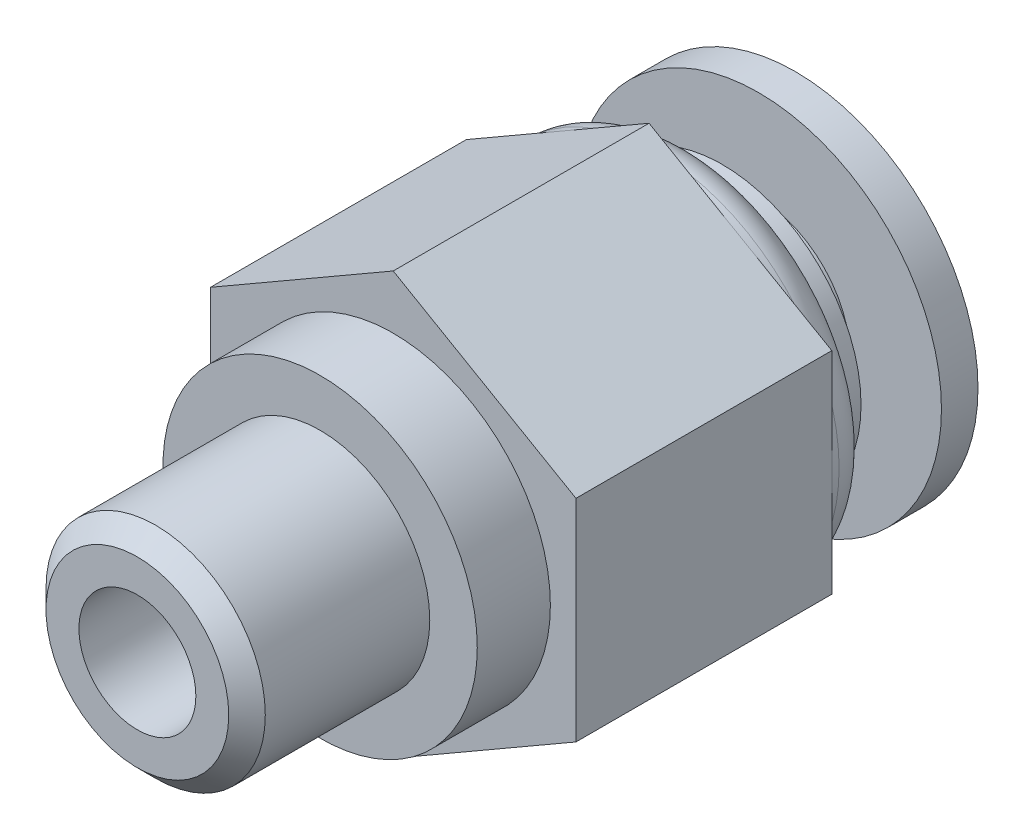
SolidWorks part; units mm, degrees
note: The reader was unsure of these and kept them because the rebuilt part matched: shared geometry of "Эскиз1<4>", "Эскиз1<5>", "Эскиз1<6>", "Эскиз1<8>", "Эскиз1<10>", "Эскиз1<11>".
material "Plain Carbon Steel"
ref_plane "Спереди" through (0, 0, 0) normal (0, 0, 1) x (1, 0, 0)
ref_plane "Сверху" through (0, 0, 0) normal (0, 1, 0) x (1, 0, 0)
ref_plane "Справа" through (0, 0, 0) normal (1, 0, 0) x (0, 0, -1)
sketch "Эскиз1" plane through (0, 0, 0) normal (0, 0, 1) x (1, 0, 0)
  line L3 (0, 5.7735) -> (-5, 2.8868)
  line L4 (-5, 2.8868) -> (-5, -2.8868)
  line L5 (-5, -2.8868) -> (0, -5.7735)
  line L6 (0, -5.7735) -> (5, -2.8868)
  line L7 (5, -2.8868) -> (5, 2.8868)
  line L8 (5, 2.8868) -> (0, 5.7735)
  circle A0 centre (0, 0) radius 1.6
  circle A1 centre (0, 0) radius 3
  circle A2 centre (0, 0) radius 5 construction
  circle A3 centre (0, 0) radius 5
  circle A4 centre (0, 0) radius 4.3
  circle A5 centre (0, 0) radius 3
  circle A6 centre (0, 0) radius 3.8
  dimension "D1" = 3.2
  dimension "D2" = 6
  dimension "D3" = 6
  dimension "D4" = 8.6
  dimension "D5" = 10
  dimension "D6" = 10
extrude "Бобышка-Вытянуть2" add sketch "Эскиз1" along normal blind 7 contours L3 L4 L5 L6 L7 L8
extrude "Бобышка-Вытянуть3" add sketch "Эскиз1<4>" against normal blind 1.2 contours A3
sketch "Эскиз1<4>" plane through (0, 0, 0) normal (0, 0, 1) x (1, 0, 0) same geometry as "Эскиз1"
extrude "Бобышка-Вытянуть4" add sketch "Эскиз1<5>" along normal blind 14 contours A5
sketch "Эскиз1<5>" plane through (0, 0, 0) normal (0, 0, 1) x (1, 0, 0) same geometry as "Эскиз1"
cosmetic thread "Условное изображение резьбы1" parameters "D2"=4.891
extrude "Бобышка-Вытянуть5" add sketch "Эскиз1<6>" along normal blind 9 contours A4
sketch "Эскиз1<6>" plane through (0, 0, 0) normal (0, 0, 1) x (1, 0, 0) same geometry as "Эскиз1"
extrude "Бобышка-Вытянуть6" add sketch "Эскиз1<8>" against normal blind 2 contours A6
sketch "Эскиз1<8>" plane through (0, 0, 0) normal (0, 0, 1) x (1, 0, 0) same geometry as "Эскиз1"
fillet "Скругление1" radius 1 1 edges at (5, 0, -1.2)
extrude "Вырез-Вытянуть31" cut sketch "Эскиз1<10>" along normal through all from offset 2 contours A0 offset against normal yes
sketch "Эскиз1<10>" plane through (0, 0, 0) normal (0, 0, 1) x (1, 0, 0) same geometry as "Эскиз1"
extrude "Вырез-Вытянуть32" cut sketch "Эскиз1<11>" along normal blind 7 from offset 2 contours A1 offset against normal yes
sketch "Эскиз1<11>" plane through (0, 0, 0) normal (0, 0, 1) x (1, 0, 0) same geometry as "Эскиз1"
chamfer "Фаска1" distance 0.5 angle 45 1 edges at (3, 0, 14)
ref_plane "Плоскость1" through (0, 0, 0) normal (1, 0, 0) x (0, 0, -1)
sketch "Эскиз3" plane through (0, 0, 0) normal (1, 0, 0) x (0, 0, -1)
  line L0 (-1.3173, 0) -> (-26.6862, 0) construction
  line L1 (4, 2) -> (4, 5)
  line L2 (3, 5) -> (3, 2.5)
  line L3 (3, 2.5) -> (-5, 2.5)
  line L4 (-5, 2.5) -> (-5, 2)
  line L5 (-5, 0) -> (4, 0) construction
  line L6 (4, 2) -> (-5, 2)
  line L7 (4, 5) -> (3, 5)
  line L9 (-14, 2.5) -> (-14, -2.5) construction
  line L10 (4, 2) -> (4, 0) construction
  line L11 (-5, 2) -> (-5, 0) construction
  dimension "D1" = 10
  dimension "D2" = 5
  dimension "D3" = 1
  dimension "D4" = 8
  dimension "D5" = 4
  dimension "D6" = 4
  dimension "D7" = 18
surface "Поверхность-Повернуть1" sketch "Эскиз3" parameters "D1"=360
